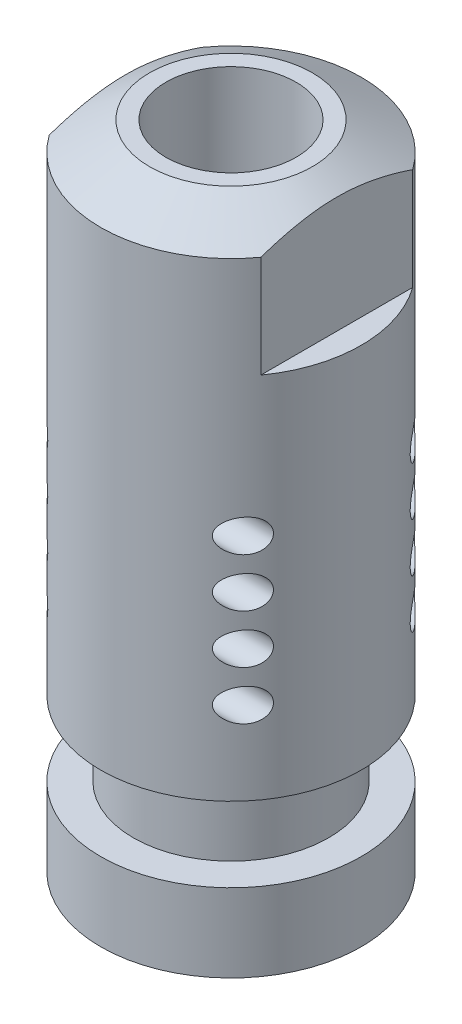
SolidWorks part; units mm, degrees
ref_plane "정면" through (0, 0, 0) normal (0, 0, 1) x (1, 0, 0)
ref_plane "윗면" through (0, 0, 0) normal (0, 1, 0) x (1, 0, 0)
ref_plane "우측면" through (0, 0, 0) normal (1, 0, 0) x (0, 0, -1)
sketch "스케치1" plane through (0, 0, 0) normal (0, 1, 0) x (1, 0, 0)
  circle A0 centre (0, 0) radius 8
  circle A1 centre (0, 0) radius 6
  dimension "D1" = 12
  dimension "D2" = 16
extrude "보스-돌출1" add sketch "스케치1" along normal blind 40 contours A1 | A0 A1 region at (-7.7737, 0, 0) region at (0, 0, 0)
extrude "컷-돌출1" cut sketch "스케치1<3>" along normal blind 4.6 from offset 4.8
sketch "스케치1<3>" plane through (0, 0, 0) normal (0, 1, 0) x (1, 0, 0) same geometry as "스케치1"
sketch "스케치3" plane through (0, 0, 0) normal (1, 0, 0) x (0, 0, -1)
  line L0 (0, 40) -> (0, 0) construction
  line L1 (8, 40) -> (-8, 40) construction
  line L2 (-8, 40) -> (-8, 38.2679)
  line L3 (-8, 40) -> (-8, 9.4) construction
  line L4 (8, 40) -> (8, 38.2679)
  line L5 (-8, 38.2679) -> (-5, 40)
  line L6 (8, 38.2679) -> (5, 40)
  line L7 (-5, 40) -> (-8, 40)
  line L8 (5, 40) -> (8, 40)
  dimension "D1" = 30
  dimension "D2" = 10
revolve "컷-회전1" cut sketch "스케치3" angle 360 about L0
sketch "스케치4" plane through (0, 40, 0) normal (0, 1, 0) x (1, 0, 0)
  line L0 (0, 8) -> (0, -8.0794) construction
  line L1 (-6.5, 4.6637) -> (-6.5, -4.6637)
  line L2 (6.5, 4.6637) -> (6.5, -4.6637)
  arc A0 (6.5, -4.6637) -> (6.5, 4.6637) centre (0, 0) ccw
  circle A1 centre (0, 0) radius 8
  arc A2 (-6.5, 4.6637) -> (-6.5, -4.6637) centre (0, 0) ccw
  circle A3 centre (0, 0) radius 4
  dimension "D3" = 8
  dimension "D2" = 13
  dimension "D1" = 0
extrude "컷-돌출2" cut sketch "스케치4" against normal blind 8 contours L1 A2 | L2 A0 region at (-7.1051, 40, 0) region at (7.1051, 40, 0)
extrude "컷-돌출3" cut sketch "스케치4<3>" against normal blind 11.5 contours A3 L0 | L0 A3 region at (1.6977, 40, 0) region at (-1.6977, 40, 0)
sketch "스케치4<3>" plane through (0, 40, 0) normal (0, 1, 0) x (1, 0, 0) same geometry as "스케치4"
sketch "스케치5" plane through (0, 0, 0) normal (1, 0, 0) x (0, 0, -1)
  line L0 (0, 40) -> (0, 0) construction
  line L1 (4, 40) -> (-4, 40) construction
  line L3 (-5.2, 23.5) -> (-5.2, 14.5) construction
  line L4 (-8, 38.2679) -> (-8, 9.4) construction
  circle A0 centre (-5.2, 23.5) radius 1
  circle A1 centre (-5.2, 20.5) radius 1
  circle A2 centre (-5.2, 17.5) radius 1
  circle A3 centre (-5.2, 14.5) radius 1
  circle A4 centre (5.2, 14.5) radius 1
  circle A5 centre (5.2, 17.5) radius 1
  circle A6 centre (5.2, 20.5) radius 1
  circle A7 centre (5.2, 23.5) radius 1
  point P21 (-5.2, 24.5)
  point P22 (-6.2, 23.5)
  dimension "D1" = 2
  dimension "D3" = 15.5
  dimension "D4" = 2.8
  dimension "D2" = 4
extrude "컷-돌출4" cut sketch "스케치5" against normal through all both and the other way through all
sketch "스케치6" plane through (0, 0, 0) normal (0, -1, 0) x (1, 0, 0)
  circle A0 centre (0, 0) radius 3.25
  dimension "D1" = 6.5
extrude "컷-돌출5" cut sketch "스케치6" against normal blind 7.5
